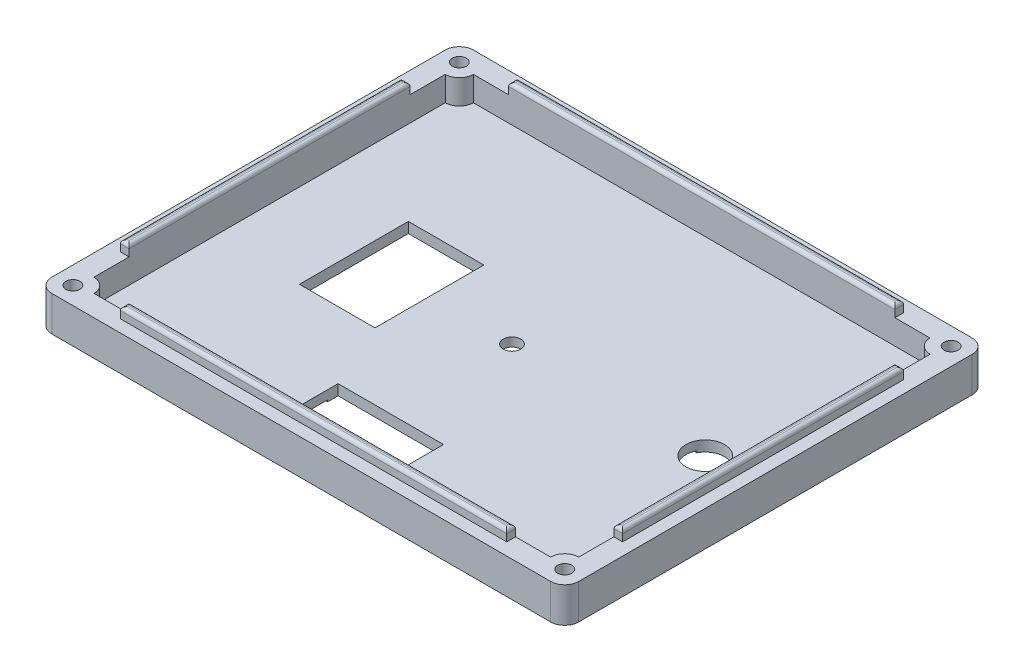
SolidWorks part; units mm, degrees
ref_plane "Alzado" through (0, 0, 0) normal (0, 0, 1) x (1, 0, 0)
ref_plane "Planta" through (0, 0, 0) normal (0, 1, 0) x (1, 0, 0)
ref_plane "Vista lateral" through (0, 0, 0) normal (1, 0, 0) x (0, 0, -1)
sketch "Croquis1" plane through (0, 0, 0) normal (0, 1, 0) x (1, 0, 0)
  line L1 (-75, -60) -> (75, -60)
  line L2 (-75, -60) -> (-75, 60)
  line L3 (-75, 60) -> (75, 60)
  line L4 (75, -60) -> (75, 60)
  line L5 (-75, -60) -> (75, 60) construction
  line L6 (-75, 60) -> (75, -60) construction
  point P0 (0, 0)
  dimension "D1" = 150
  dimension "D2" = 120
extrude "Saliente-Extruir1" add sketch "Croquis1" along normal blind 10
sketch "Croquis2" plane through (0, 10, 0) normal (0, 1, 0) x (1, 0, 0)
  line L0 (75, 60) -> (-75, 60) construction
  line L1 (-71.5, -56.5) -> (71.5, -56.5)
  line L2 (-71.5, -56.5) -> (-71.5, 56.5)
  line L3 (-71.5, 56.5) -> (71.5, 56.5)
  line L4 (71.5, -56.5) -> (71.5, 56.5)
  line L5 (-71.5, -56.5) -> (71.5, 56.5) construction
  line L6 (-71.5, 56.5) -> (71.5, -56.5) construction
  line L7 (-75, 60) -> (-75, -60) construction
  point P0 (0, 0)
  dimension "D1" = 3.5
  dimension "D2" = 3.5
extrude "Saliente-Extruir2" add sketch "Croquis2" along normal blind 3
sketch "Croquis4" plane through (0, 13, 0) normal (0, 1, 0) x (1, 0, 0)
  line L5 (-65, 54) -> (65, 54)
  line L6 (75, 60) -> (65, 60) construction
  line L8 (75, 60) -> (75, 50) construction
  line L9 (-75, 60) -> (-65, 60) construction
  line L10 (-75, 60) -> (-75, 50) construction
  line L11 (-75, 50) -> (-65, 50) construction
  line L12 (-65, 60) -> (-65, 50) construction
  line L13 (75, 50) -> (65, 50) construction
  line L14 (65, 60) -> (65, 50) construction
  line L15 (75, -60) -> (65, -60) construction
  line L16 (75, -60) -> (75, -50) construction
  line L17 (75, -50) -> (65, -50) construction
  line L18 (65, -60) -> (65, -50) construction
  line L19 (-75, -60) -> (-65, -60) construction
  line L20 (-75, -60) -> (-75, -50) construction
  line L21 (-75, -50) -> (-65, -50) construction
  line L22 (-65, -60) -> (-65, -50) construction
  line L23 (65, 54) -> (65, 50)
  line L24 (65, 50) -> (69, 50)
  line L25 (69, 50) -> (69, -50)
  line L26 (69, -50) -> (65, -50)
  line L27 (65, -50) -> (65, -54)
  line L28 (65, -54) -> (-65, -54)
  line L29 (-65, -54) -> (-65, -50)
  line L30 (-65, -50) -> (-69, -50)
  line L31 (-69, -50) -> (-69, 50)
  line L32 (-69, 50) -> (-65, 50)
  line L33 (-65, 50) -> (-65, 54)
  line L34 (-75, 60) -> (-75, -60) construction
  line L35 (75, 60) -> (-75, 60) construction
  line L36 (75, -60) -> (75, 60) construction
  line L37 (-75, -60) -> (75, -60) construction
  point P0 (0, 0)
  dimension "D1" = 6
  dimension "D2" = 6
  dimension "D3" = 10
  dimension "D4" = 10
  dimension "D5" = 10
  dimension "D6" = 10
  dimension "D7" = 6
  dimension "D8" = 6
extrude "Cortar-Extruir4" cut sketch "Croquis4" against normal offset from surface (10 mm away) 3 up to face at (0, 0, 0)
sketch "Croquis5" plane through (0, 13, 0) normal (0, 1, 0) x (1, 0, 0)
  line L1 (-75, 60) -> (-55, 60)
  line L2 (-75, 60) -> (-75, 40)
  line L3 (-75, 40) -> (-55, 40)
  line L4 (-55, 60) -> (-55, 40)
  line L5 (75, 60) -> (55, 60)
  line L6 (75, 60) -> (75, 40)
  line L7 (75, 40) -> (55, 40)
  line L8 (55, 60) -> (55, 40)
  line L9 (75, -60) -> (55, -60)
  line L10 (75, -60) -> (75, -40)
  line L11 (75, -40) -> (55, -40)
  line L12 (55, -60) -> (55, -40)
  line L13 (-75, -60) -> (-55, -60)
  line L14 (-75, -60) -> (-75, -40)
  line L15 (-75, -40) -> (-55, -40)
  line L16 (-55, -60) -> (-55, -40)
  dimension "D1" = 20
  dimension "D2" = 20
  dimension "D3" = 20
  dimension "D4" = 20
extrude "Cortar-Extruir5" cut sketch "Croquis5" against normal up to surface (3 mm away) up to face at (0, 10, 0)
sketch "Croquis7" plane through (0, 10, 0) normal (0, 1, 0) x (1, 0, 0)
  line L1 (-75, 60) -> (-65, 60) construction
  line L2 (-75, 60) -> (-75, 50) construction
  line L3 (-75, 50) -> (-65, 50) construction
  line L4 (-65, 60) -> (-65, 50) construction
  line L5 (-75, 60) -> (-65, 50) construction
  line L6 (-75, 50) -> (-65, 60) construction
  line L7 (75, 60) -> (65, 60) construction
  line L8 (75, 60) -> (75, 50) construction
  line L9 (75, 50) -> (65, 50) construction
  line L10 (65, 60) -> (65, 50) construction
  line L11 (75, 60) -> (65, 50) construction
  line L12 (75, 50) -> (65, 60) construction
  line L13 (75, -60) -> (65, -60) construction
  line L14 (75, -60) -> (75, -50) construction
  line L15 (75, -50) -> (65, -50) construction
  line L16 (65, -60) -> (65, -50) construction
  line L17 (75, -60) -> (65, -50) construction
  line L18 (75, -50) -> (65, -60) construction
  line L19 (-75, -60) -> (-65, -60) construction
  line L20 (-75, -60) -> (-75, -50) construction
  line L21 (-75, -50) -> (-65, -50) construction
  line L22 (-65, -60) -> (-65, -50) construction
  line L23 (-75, -60) -> (-65, -50) construction
  line L24 (-75, -50) -> (-65, -60) construction
  circle A0 centre (-70, 55) radius 2
  circle A1 centre (70, 55) radius 2
  circle A2 centre (70, -55) radius 2
  circle A3 centre (-70, -55) radius 2
  point P0 (-70, 55)
  point P6 (70, 55)
  point P12 (70, -55)
  point P18 (-70, -55)
  dimension "D1" = 4
extrude "Cortar-Extruir6" cut sketch "Croquis7" against normal through all
chamfer "Chaflán1" distance 4 angle 30 4 edges at (-70, 0, -53) (-70, 0, 57) (70, 0, 57) (70, 0, -53) first distance on face at (-70, 0, -53) first distance on face at (-70, 0, 57) first distance on face at (70, 0, 57) first distance on face at (70, 0, -53)
fillet "Redondeo3" radius 4 4 edges at (75, 5, 60) (75, 5, -60) (-75, 5, -60) (-75, 5, 60)
fillet "Redondeo4" radius 4 4 edges at (65, 6.5, -50) (65, 6.5, 50) (-65, 6.5, 50) (-65, 6.5, -50)
fillet "Redondeo5" radius 1 16 edges at (-70.25, 13, -40) (-69, 13, 0) (-70.25, 13, 40) (-71.5, 13, 0) (70.25, 13, 40) (70.25, 13, -40) (55, 13, -55.25) (-55, 13, -55.25) (0, 13, -54) (0, 13, -56.5) (71.5, 13, 0) (69, 13, 0) (55, 13, 55.25) (0, 13, 54) (0, 13, 56.5) (-55, 13, 55.25)
sketch "Croquis8" plane through (0, 0, 0) normal (0, -1, 0) x (1, 0, 0)
  line L0 (-75, -56) -> (-75, 56) construction
  line L1 (-45, -15.5) -> (-23.5, -15.5)
  line L2 (-45, -15.5) -> (-45, 15.5)
  line L3 (-45, 15.5) -> (-23.5, 15.5)
  line L4 (-23.5, -15.5) -> (-23.5, 15.5)
  line L5 (-45, -15.5) -> (-23.5, 15.5) construction
  line L6 (-45, 15.5) -> (-23.5, -15.5) construction
  line L12 (75, 56) -> (75, -56) construction
  line L13 (-71, 60) -> (71, 60) construction
  line L16 (-15, 34.5) -> (15, 34.5)
  line L17 (-15, 34.5) -> (-15, 45.5)
  line L18 (-15, 45.5) -> (15, 45.5)
  line L19 (15, 34.5) -> (15, 45.5)
  line L20 (-15, 34.5) -> (15, 45.5) construction
  line L21 (-15, 45.5) -> (15, 34.5) construction
  circle A0 centre (0, 0) radius 2.5
  circle A1 centre (55, 0) radius 5.5
  point P0 (-34.25, 0)
  point P19 (0, 40)
  dimension "D6" = 5
  dimension "D4" = 11
  dimension "D1" = 31
  dimension "D2" = 21.5
  dimension "D3" = 30
  dimension "D5" = 20
  dimension "D7" = 20
  dimension "D9" = 30
  dimension "D10" = 11
extrude "Cortar-Extruir7" cut sketch "Croquis8" against normal through all
sketch "Croquis9" plane through (0, 0, 0) normal (0, -1, 0) x (1, 0, 0)
  line L0 (-23.5, 2.5) -> (-23.5, -2.5)
  line L5 (-23.5, -15.5) -> (-23.5, 15.5) construction
  line L6 (-23.5, -2.5) -> (-12.5, -2.5)
  line L7 (-12.5, -2.5) -> (-12.5, -12.5)
  line L8 (-12.5, -12.5) -> (12.5, -12.5)
  line L9 (12.5, -12.5) -> (12.5, -2.5)
  line L10 (-23.5, 2.5) -> (-20.5, 2.5)
  line L11 (-12.5, 2.5) -> (-12.5, 12.5)
  line L12 (-12.5, 12.5) -> (12.5, 12.5)
  line L13 (12.5, 12.5) -> (12.5, 2.5)
  line L14 (-20.5, 2.5) -> (-20.5, 42.5)
  line L18 (-15.5, 37.5) -> (-15.5, 2.5)
  line L19 (-15.5, 2.5) -> (-12.5, 2.5)
  line L20 (50.101, 2.5) -> (20.5, 2.5)
  line L21 (20.5, 2.5) -> (20.5, 42.5)
  line L22 (20.5, 42.5) -> (-20.5, 42.5)
  line L24 (-15.5, 37.5) -> (15.5, 37.5)
  line L25 (15.5, 37.5) -> (15.5, 2.5)
  line L26 (15.5, 2.5) -> (12.5, 2.5)
  line L27 (12.5, -2.5) -> (50.101, -2.5)
  line L28 (50.101, -2.5) -> (50.101, 2.5)
  line L29 (-45, 15.5) -> (-45, -15.5) construction
  line L30 (-15.5, 37.5) -> (-15.5, 42.5) construction
  line L31 (-15, 45.5) -> (-15, 34.5) construction
  line L32 (0, -12.5) -> (0, 12.5) construction
  circle A0 centre (55, 0) radius 5.5 construction
  point P5 (-23.5, 0)
  point P15 (-15.5, 40)
  point P18 (-45, 0)
  point P26 (-15, 40)
  point P33 (0, 0)
  dimension "D1" = 5
  dimension "D2" = 5
  dimension "D3" = 5
  dimension "D4" = 5
  dimension "D5" = 25
  dimension "D6" = 25
extrude "Cortar-Extruir8" cut sketch "Croquis9" against normal blind 0.5
